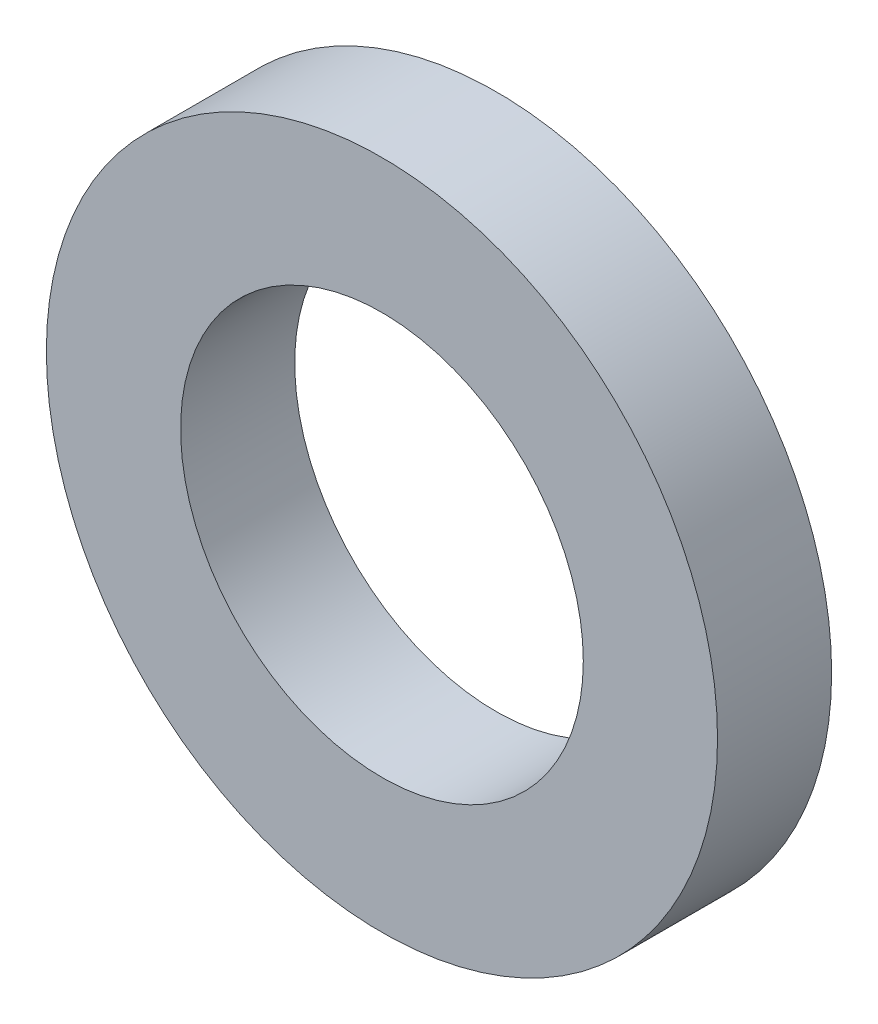
SolidWorks part; units mm, degrees
ref_plane "Front Plane" through (0, 0, 0) normal (0, 0, 1) x (1, 0, 0)
ref_plane "Top Plane" through (0, 0, 0) normal (0, 1, 0) x (1, 0, 0)
ref_plane "Right Plane" through (0, 0, 0) normal (1, 0, 0) x (0, 0, -1)
sketch "Sketch1" plane through (0, 0, 0) normal (0, 0, 1) x (1, 0, 0)
  circle A0 centre (0, 0) radius 3
  circle A1 centre (0, 0) radius 5
  dimension "D1" = 6
  dimension "D2" = 10
extrude "Boss-Extrude1" add sketch "Sketch1" along normal blind 1.7
equation "\"smallPulleyTeeth\"= 15"
equation "\"largePulleyTeeth\"= 30"
equation "\"eighthThick\"= 2.9mm"
equation "\"sixteenthThick\" = 1.7mm"
equation "\"quarterThick\"=5.6mm"
equation "\"OD\" = 150mm"
equation "\"puckAngle\" = 60.5deg"
equation "\"puckDiam\" = 76.5mm"
equation "\"axlePress\" = 5.8mm"
equation "\"press\" = 0.2mm"
equation "\"wheelClear\" = 0.3mm"
equation "\"10-32clear\" = 4.5mm"
equation "\"6-32clear\" = 3.3mm"
equation "\"8-32clear\" = 4.0mm"
equation "\"D1@Boss-Extrude1\"=\"sixteenthThick\""
